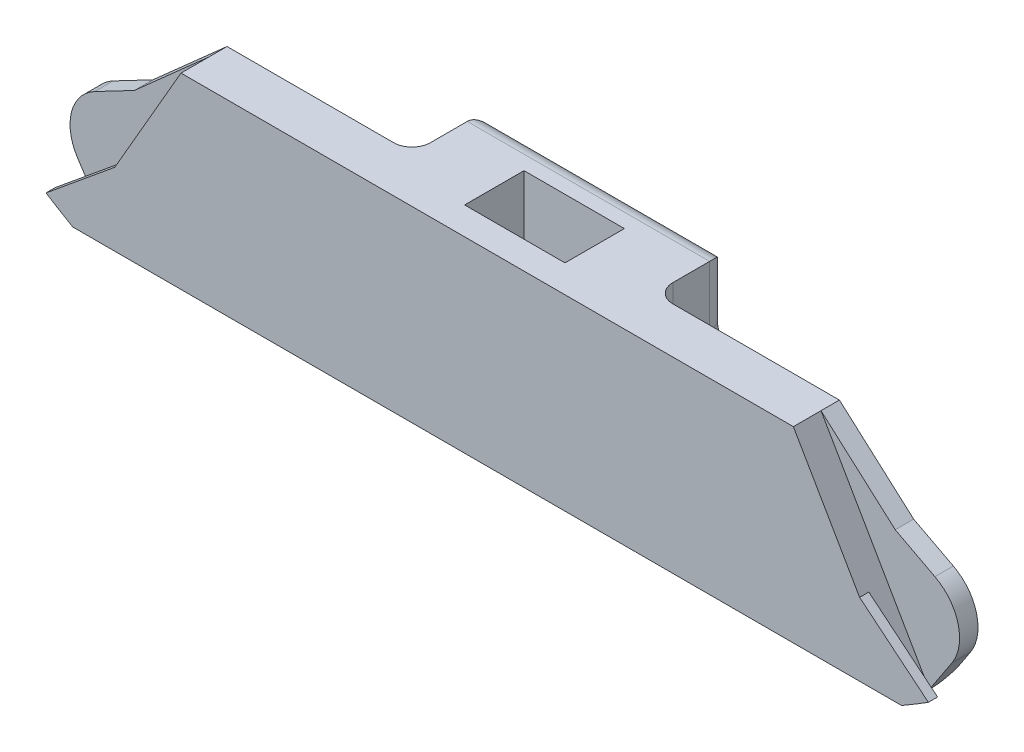
SolidWorks part; units mm, degrees
ref_plane "Alzado" through (0, 0, 0) normal (0, 0, 1) x (1, 0, 0)
ref_plane "Planta" through (0, 0, 0) normal (0, 1, 0) x (1, 0, 0)
ref_plane "Vista lateral" through (0, 0, 0) normal (1, 0, 0) x (0, 0, -1)
sketch "Croquis1" plane through (0, 0, 0) normal (0, 0, 1) x (1, 0, 0)
  line L4 (-45, -77.9423) -> (-40.4434, -70.0501)
  line L5 (-40.4434, -70.0501) -> (-47.9091, -76.1887)
  line L6 (-45, -77.9423) -> (-40.4434, -70.0501)
  line L7 (-40.4434, -70.0501) -> (-47.9091, -76.1887)
  line L10 (40.4434, -70.0501) -> (45, -77.9423)
  line L11 (47.9091, -76.1887) -> (40.4434, -70.0501)
  line L12 (40.4434, -70.0501) -> (45, -77.9423)
  line L13 (47.9091, -76.1887) -> (40.4434, -70.0501)
  arc A2 (-47.9091, -76.1887) -> (-45, -77.9423) centre (0, 0) ccw
  arc A3 (-47.9091, -76.1887) -> (-45, -77.9423) centre (0, 0) ccw
  arc A5 (45, -77.9423) -> (47.9091, -76.1887) centre (0, 0) ccw
  arc A6 (45, -77.9423) -> (47.9091, -76.1887) centre (0, 0) ccw
  dimension "D1" = 0
  dimension "D2" = 0
extrude "Saliente-Extruir1" add sketch "Croquis1" along normal up to surface (1 mm away)
sketch "Croquis2" plane through (0, 0, 1) normal (0, 0, 1) x (1, 0, 0)
  line L0 (33.25, -57.5907) -> (-33.25, -57.5907)
  line L1 (-33.25, -57.5907) -> (-45, -77.9423)
  line L2 (-45, -77.9423) -> (45, -77.9423)
  line L3 (45, -77.9423) -> (33.25, -57.5907)
extrude "Saliente-Extruir2" add sketch "Croquis2" against normal up to surface (3 mm away)
sketch "Croquis3" plane through (0, 0, -2) normal (0, 0, -1) x (-1, 0, 0)
  line L0 (0, -57.5907) -> (0, -77.9423) construction
  line L1 (33.25, -57.5907) -> (-33.25, -57.5907) construction
  line L2 (-45, -77.9423) -> (45, -77.9423) construction
  line L3 (6.325, -77.9423) -> (6.325, -70.1423)
  line L5 (6.325, -70.1423) -> (5.45, -70.1423)
  line L6 (5.45, -70.1423) -> (5.45, -57.5907)
  line L7 (5.45, -57.5907) -> (13.1616, -57.5907)
  line L8 (13.1616, -57.5907) -> (13.1616, -64.7573)
  line L9 (13.1616, -64.7573) -> (18.3009, -72.1471)
  line L10 (18.3009, -72.1471) -> (18.3009, -77.9423)
  line L11 (6.325, -77.9423) -> (18.3009, -77.9423)
  line L12 (-6.325, -77.9423) -> (-6.325, -70.1423)
  line L13 (-6.325, -70.1423) -> (-5.45, -70.1423)
  line L14 (-5.45, -70.1423) -> (-5.45, -57.5907)
  line L15 (-5.45, -57.5907) -> (-13.1616, -57.5907)
  line L16 (-13.1616, -57.5907) -> (-13.1616, -64.7573)
  line L17 (-13.1616, -64.7573) -> (-18.3009, -72.1471)
  line L18 (-18.3009, -72.1471) -> (-18.3009, -77.9423)
  line L19 (-6.325, -77.9423) -> (-18.3009, -77.9423)
  line L20 (45, -77.9423) -> (-45, -77.9423) construction
  dimension "D1" = 12.65
  dimension "D2" = 10.9
  dimension "D3" = 7.8
extrude "Saliente-Extruir3" add sketch "Croquis3" along normal blind 6.45
sketch "Croquis4" plane through (0, 0, -8.45) normal (0, 0, -1) x (-1, 0, 0)
  line L16 (18.3009, -77.9423) -> (18.3009, -72.1471)
  line L17 (18.3009, -72.1471) -> (13.1616, -64.7573)
  line L18 (13.1616, -64.7573) -> (13.1616, -57.5907)
  line L19 (13.1616, -57.5907) -> (5.45, -57.5907)
  line L20 (5.45, -57.5907) -> (5.45, -70.1423)
  line L21 (5.45, -70.1423) -> (6.325, -70.1423)
  line L22 (6.325, -70.1423) -> (6.325, -77.9423)
  line L23 (6.325, -77.9423) -> (18.3009, -77.9423)
  line L24 (18.3009, -77.9423) -> (18.3009, -72.1471)
  line L25 (18.3009, -72.1471) -> (13.1616, -64.7573)
  line L26 (13.1616, -64.7573) -> (13.1616, -57.5907)
  line L31 (6.325, -77.9423) -> (18.3009, -77.9423)
  line L32 (13.1616, -57.5907) -> (-13.1616, -57.5907)
  line L33 (6.325, -77.9423) -> (-6.325, -77.9423)
  line L40 (-6.325, -77.9423) -> (-6.325, -70.1423)
  line L41 (-6.325, -70.1423) -> (-5.45, -70.1423)
  line L42 (-5.45, -70.1423) -> (-5.45, -57.5907)
  line L43 (-5.45, -57.5907) -> (-13.1616, -57.5907)
  line L44 (-13.1616, -57.5907) -> (-13.1616, -64.7573)
  line L45 (-13.1616, -64.7573) -> (-18.3009, -72.1471)
  line L46 (-18.3009, -72.1471) -> (-18.3009, -77.9423)
  line L47 (-18.3009, -77.9423) -> (-6.325, -77.9423)
  line L52 (-13.1616, -57.5907) -> (-13.1616, -64.7573)
  line L53 (-13.1616, -64.7573) -> (-18.3009, -72.1471)
  line L54 (-18.3009, -72.1471) -> (-18.3009, -77.9423)
  line L55 (-18.3009, -77.9423) -> (-6.325, -77.9423)
  line M20 (18.3009, -77.9423) -> (18.3009, -72.1471)
  line M21 (18.3009, -72.1471) -> (13.1616, -64.7573)
  line M22 (13.1616, -64.7573) -> (13.1616, -57.5907)
  line M23 (13.1616, -57.5907) -> (5.45, -57.5907)
  line M24 (5.45, -57.5907) -> (5.45, -70.1423)
  line M25 (5.45, -70.1423) -> (6.325, -70.1423)
  line M26 (6.325, -70.1423) -> (6.325, -77.9423)
  line M27 (6.325, -77.9423) -> (18.3009, -77.9423)
  dimension "D1" = 0
  dimension "D2" = 0
extrude "Saliente-Extruir4" add sketch "Croquis4" along normal up to surface (3.55 mm away) contours M27 M20 M21 M22 M23 M24 M25 M26 | L54 L55 L33 L32 L52 L53 M26 M25 M24
sketch "Croquis5" plane through (0, 0, -2) normal (0, 0, -1) x (-1, 0, 0)
  line L20 (13.1616, -57.5907) -> (13.1616, -64.7573)
  line L21 (13.1616, -64.7573) -> (18.3009, -72.1471)
  line L22 (18.3009, -72.1471) -> (18.3009, -77.9423)
  line L23 (18.3009, -77.9423) -> (45, -77.9423)
  line L24 (45, -77.9423) -> (33.25, -57.5907)
  line L25 (33.25, -57.5907) -> (13.1616, -57.5907)
  line L26 (13.1616, -57.5907) -> (13.1616, -64.7573)
  line L27 (13.1616, -64.7573) -> (18.3009, -72.1471)
  line L28 (18.3009, -72.1471) -> (18.3009, -77.9423)
  line L29 (18.3009, -77.9423) -> (45, -77.9423)
  line L31 (33.25, -57.5907) -> (13.1616, -57.5907)
  line L32 (-33.25, -57.5907) -> (-41.3154, -64.7573)
  line L33 (-41.3154, -64.7573) -> (-45.6203, -67.0122)
  line L34 (-47.4731, -74.196) -> (-45, -77.9423)
  line L35 (0, -57.5907) -> (0, -77.9423) construction
  line L36 (13.1616, -57.5907) -> (-13.1616, -57.5907) construction
  line L37 (-18.3009, -77.9423) -> (18.3009, -77.9423) construction
  line L38 (-18.3009, -77.9423) -> (-18.3009, -72.1471)
  line L39 (-18.3009, -72.1471) -> (-13.1616, -64.7573)
  line L40 (-13.1616, -64.7573) -> (-13.1616, -57.5907)
  line L41 (-13.1616, -57.5907) -> (-33.25, -57.5907)
  line L42 (-33.25, -57.5907) -> (-45, -77.9423)
  line L43 (-45, -77.9423) -> (-18.3009, -77.9423)
  line L44 (-18.3009, -77.9423) -> (-18.3009, -72.1471)
  line L45 (-18.3009, -72.1471) -> (-13.1616, -64.7573)
  line L46 (-13.1616, -64.7573) -> (-13.1616, -57.5907)
  line L47 (-13.1616, -57.5907) -> (-33.25, -57.5907)
  line L49 (-45, -77.9423) -> (-18.3009, -77.9423)
  line L50 (47.4731, -74.196) -> (45, -77.9423)
  line L51 (41.3154, -64.7573) -> (45.6203, -67.0122)
  line L52 (33.25, -57.5907) -> (41.3154, -64.7573)
  arc A0 (47.4731, -74.196) -> (45.6203, -67.0122) centre (43.3003, -71.4414) ccw
  arc A1 (-45.6203, -67.0122) -> (-47.4731, -74.196) centre (-43.3003, -71.4414) ccw
  point P24 (50.5209, -69.5791)
  point P27 (-50.5209, -69.5791)
  dimension "D3" = 5
  dimension "D1" = 0
  dimension "D2" = 0
extrude "Saliente-Extruir5" add sketch "Croquis5" along normal blind 2
fillet "Redondeo1" radius 2 22 edges at (31.6504, -77.9423, -4) (-18.3009, -77.9423, -8) (18.3009, -75.0447, -12) (18.3009, -77.9423, -8) (0, -57.5907, -12) (0, -77.9423, -12) (-31.6504, -77.9423, -4) (-18.3009, -72.1471, -8) (-13.1616, -64.7573, -8) (13.1616, -64.7573, -8) (18.3009, -72.1471, -8) (15.7312, -68.4522, -12) (13.1616, -61.174, -12) (13.1616, -61.174, -4) (15.7312, -68.4522, -4) (18.3009, -75.0447, -4) (-18.3009, -75.0447, -12) (-15.7312, -68.4522, -12) (-13.1616, -61.174, -12) (-13.1616, -61.174, -4) (-15.7312, -68.4522, -4) (-18.3009, -75.0447, -4)
